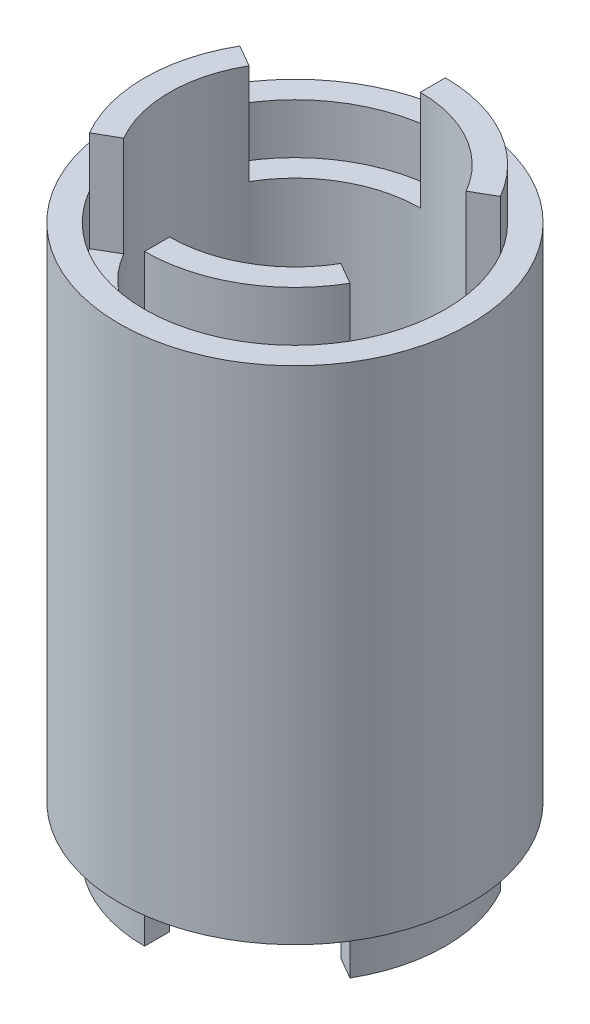
SolidWorks part; units mm, degrees
ref_plane "Front Plane" through (0, 0, 0) normal (0, 0, 1) x (1, 0, 0)
ref_plane "Top Plane" through (0, 0, 0) normal (0, 1, 0) x (1, 0, 0)
ref_plane "Right Plane" through (0, 0, 0) normal (1, 0, 0) x (0, 0, -1)
sketch "Sketch1" plane through (0, 0, 0) normal (0, 1, 0) x (1, 0, 0)
  circle A2 centre (0, 0) radius 15
  circle A3 centre (0, 0) radius 12.5
  dimension "D2" = 30
  dimension "D3" = 25
extrude "Boss-Extrude1" add sketch "Sketch1" along normal mid plane 35 contours A2 A3 region at (-14.5757, 0, 0)
sketch "Sketch2" plane through (0, 0, 0) normal (0, 1, 0) x (1, 0, 0)
  circle A0 centre (0, 0) radius 17.5
  circle A1 centre (0, 0) radius 15 construction
  circle A2 centre (0, 0) radius 15
  dimension "D1" = 35
extrude "Boss-Extrude2" add sketch "Sketch2" along normal mid plane 50
sketch "Sketch3" plane through (0, -17.5, 0) normal (0, -1, 0) x (1, 0, 0)
  circle A0 centre (0, 0) radius 12.5 construction
  circle A1 centre (0, 0) radius 15
  circle A2 centre (0, 0) radius 15
  circle A3 centre (0, 0) radius 12.5
  dimension "D1" = 0
extrude "Boss-Extrude3" add sketch "Sketch3" along normal blind 12.5
sketch "Sketch4" plane through (0, 17.5, 0) normal (0, 1, 0) x (1, 0, 0)
  line L0 (0, 12.5) -> (0, 15)
  line L2 (10.8253, 6.25) -> (12.9904, 7.5)
  line L4 (10.8253, -6.25) -> (12.9904, -7.5)
  line L6 (0, -12.5) -> (0, -15)
  line L8 (-10.8253, -6.25) -> (-12.9904, -7.5)
  line L10 (-10.8253, 6.25) -> (-12.9904, 7.5)
  line L12 (0, 0) -> (-7.5, 12.9904) [skipped]
  line L13 (0, 0) -> (-7.5, -12.9904) [skipped]
  line L14 (0, 0) -> (15, 0) [skipped]
  line L15 (-12.5, 0) -> (-15, 0) [skipped]
  line L16 (6.25, 10.8253) -> (7.5, 12.9904) [skipped]
  line L17 (6.25, -10.8253) -> (7.5, -12.9904) [skipped]
  circle A0 centre (0, 0) radius 15 construction
  circle A1 centre (0, 0) radius 15 construction
  arc A2 (-12.9904, 7.5) -> (-12.9904, -7.5) centre (0, 0) ccw
  arc A3 (0, -15) -> (12.9904, -7.5) centre (0, 0) ccw
  arc A4 (12.9904, 7.5) -> (0, 15) centre (0, 0) ccw
  circle A5 centre (0, 0) radius 12.5 construction
  arc A6 (10.8253, 6.25) -> (0, 12.5) centre (0, 0) ccw
  arc A7 (-10.8253, 6.25) -> (-10.8253, -6.25) centre (0, 0) ccw
  arc A8 (0, -12.5) -> (10.8253, -6.25) centre (0, 0) ccw
  point P20 (0, 0)
  dimension "D1" = 15
  dimension "D2" = 12
extrude "Boss-Extrude4" add sketch "Sketch4" along normal blind 12.5
sketch "Sketch6" plane through (0, 17.5, 0) normal (0, 1, 0) x (1, 0, 0)
  line L0 (0, -15) -> (0, -12.5) construction
  line L1 (-10.8253, -6.25) -> (-12.9904, -7.5) construction
  line L2 (-12.9904, 7.5) -> (-10.8253, 6.25)
  line L3 (0, 12.5) -> (0, 15)
  line L4 (-12.9904, 7.5) -> (-10.8253, 6.25)
  line L5 (0, 12.5) -> (0, 15)
  line L6 (10.8253, -6.25) -> (12.9904, -7.5) construction
  line L7 (12.9904, 7.5) -> (10.8253, 6.25) construction
  line L8 (0, -15) -> (0, -12.5)
  line L9 (-10.8253, -6.25) -> (-12.9904, -7.5)
  line L10 (10.8253, -6.25) -> (12.9904, -7.5)
  line L11 (12.9904, 7.5) -> (10.8253, 6.25)
  arc A0 (-12.9904, -7.5) -> (0, -15) centre (0, 0) ccw construction
  arc A1 (-10.8253, -6.25) -> (0, -12.5) centre (0, 0) ccw construction
  arc A2 (0, 15) -> (-12.9904, 7.5) centre (0, 0) ccw
  arc A3 (0, 12.5) -> (-10.8253, 6.25) centre (0, 0) ccw
  arc A4 (0, 15) -> (-12.9904, 7.5) centre (0, 0) ccw
  arc A5 (0, 12.5) -> (-10.8253, 6.25) centre (0, 0) ccw
  arc A6 (10.8253, -6.25) -> (10.8253, 6.25) centre (0, 0) ccw construction
  arc A7 (12.9904, -7.5) -> (12.9904, 7.5) centre (0, 0) ccw construction
  arc A8 (-12.9904, -7.5) -> (0, -15) centre (0, 0) ccw
  arc A9 (-10.8253, -6.25) -> (0, -12.5) centre (0, 0) ccw
  arc A10 (10.8253, -6.25) -> (10.8253, 6.25) centre (0, 0) ccw
  arc A11 (12.9904, -7.5) -> (12.9904, 7.5) centre (0, 0) ccw
  dimension "D1" = 0
extrude "Boss-Extrude6" add sketch "Sketch6" along normal blind 2.5
sketch "Sketch7" plane through (0, -30, 0) normal (0, -1, 0) x (1, 0, 0)
  line L0 (0, 12.5) -> (0, 15)
  line L2 (10.8253, 6.25) -> (12.9904, 7.5)
  line L4 (10.8253, -6.25) -> (12.9904, -7.5)
  line L6 (0, -12.5) -> (0, -15)
  line L8 (-10.8253, -6.25) -> (-12.9904, -7.5)
  line L10 (-10.8253, 6.25) -> (-12.9904, 7.5)
  line L12 (-6.25, 10.8253) -> (-7.5, 12.9904) [skipped]
  line L13 (6.25, 10.8253) -> (7.5, 12.9904) [skipped]
  line L14 (12.5, 0) -> (15, 0) [skipped]
  line L15 (6.25, -10.8253) -> (7.5, -12.9904) [skipped]
  line L16 (-6.25, -10.8253) -> (-7.5, -12.9904) [skipped]
  line L17 (-12.5, 0) -> (-15, 0) [skipped]
  circle A0 centre (0, 0) radius 12.5 construction
  circle A1 centre (0, 0) radius 15
  arc A2 (-12.9904, 7.5) -> (-12.9904, -7.5) centre (0, 0) ccw
  arc A3 (-10.8253, 6.25) -> (-10.8253, -6.25) centre (0, 0) ccw
  arc A4 (12.9904, 7.5) -> (0, 15) centre (0, 0) ccw
  arc A5 (10.8253, 6.25) -> (0, 12.5) centre (0, 0) ccw
  arc A6 (0, -15) -> (12.9904, -7.5) centre (0, 0) ccw
  arc A7 (0, -12.5) -> (10.8253, -6.25) centre (0, 0) ccw
  point P19 (0, 0)
  dimension "D1" = 0
  dimension "D2" = 12
extrude "Cut-Extrude1" cut sketch "Sketch7" against normal blind 10
